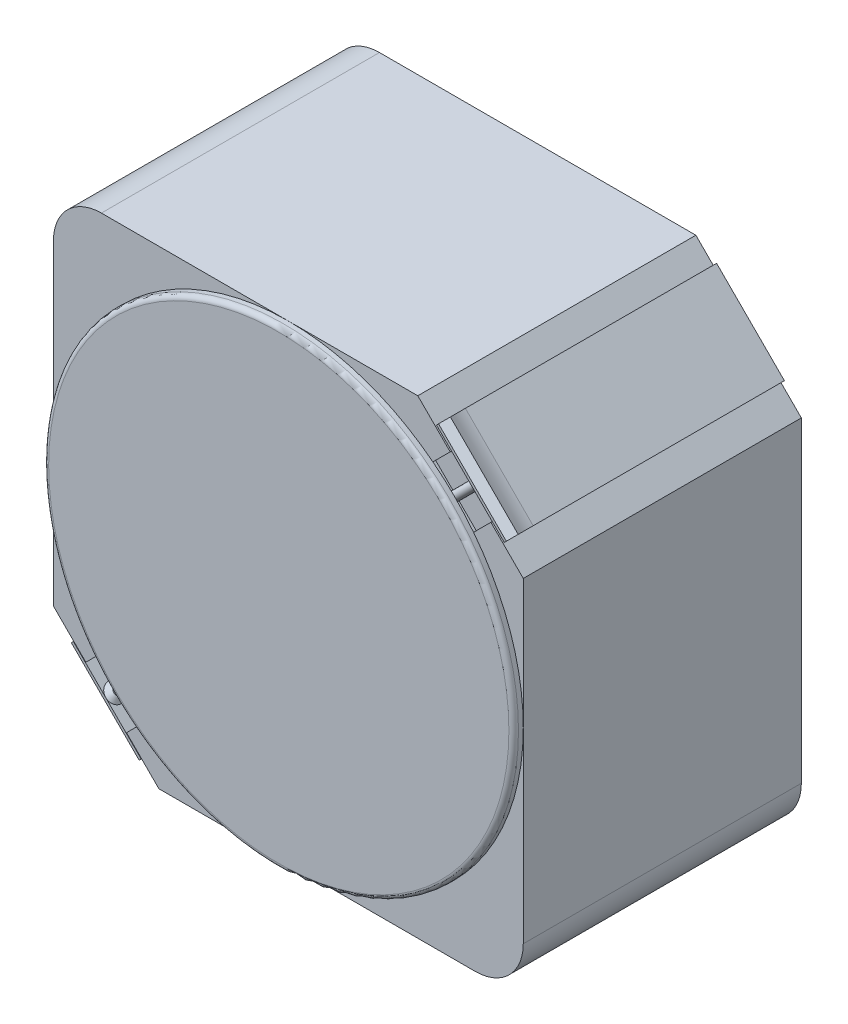
SolidWorks part; units mm, degrees
ref_plane "Спереди" through (0, 0, 0) normal (0, 0, 1) x (1, 0, 0)
ref_plane "Сверху" through (0, 0, 0) normal (0, 1, 0) x (1, 0, 0)
ref_plane "Справа" through (0, 0, 0) normal (1, 0, 0) x (0, 0, -1)
sketch "Эскиз1" plane through (0, 0, 0) normal (0, 0, 1) x (1, 0, 0)
  line L0 (-2.45, -1.35) -> (-1.35, -2.45)
  line L1 (-1.95, 2.45) -> (1.35, 2.45)
  line L2 (-2.45, 1.95) -> (-2.45, -1.35)
  line L3 (-1.35, -2.45) -> (1.95, -2.45)
  line L4 (2.45, 1.35) -> (2.45, -1.95)
  line L5 (-2.45, 2.45) -> (2.45, -2.45) construction
  line L6 (-2.45, -2.45) -> (2.45, 2.45) construction
  line L7 (1.35, 2.45) -> (2.45, 1.35)
  arc A0 (-1.95, 2.45) -> (-2.45, 1.95) centre (-1.95, 1.95) ccw
  arc A1 (1.95, -2.45) -> (2.45, -1.95) centre (1.95, -1.95) ccw
  point P0 (0, 0)
  dimension "D1" = 0.5
  dimension "D2" = 4.9
extrude "Корпус" add sketch "Эскиз1" along normal blind 2.9 from offset 0.005
sketch "Эскиз2" plane through (0, 0, 2.905) normal (0, 0, 1) x (1, 0, 0)
  line L0 (-2.45, 1.95) -> (-2.45, -1.35) construction
  circle A0 centre (0, 0) radius 2.45
extrude "Серлечник" add sketch "Эскиз2" along normal blind 0.1 and the other way blind 1
fillet "Скругление1" radius 0.05 1 edges at (2.45, 0, 3.005)
ref_plane "Плоскость1" through (0.55, -0.55, 0) normal (0.7071, -0.7071, 0) x (0, 0, 1)
sketch "Эскиз6" plane through (0.55, -0.55, 0) normal (0.7071, -0.7071, 0) x (0, 0, 1)
  line L0 (2.813, -2.782) -> (2.9, -2.73)
  line L1 (2.9, -2.7) -> (0.03, -2.7)
  line L2 (2.62, -2.73) -> (0, -2.73)
  line L3 (0, -2.73) -> (0, -2.2)
  line L4 (0.03, -2.7) -> (0.03, -2.2)
  line L5 (0.03, -2.2) -> (0, -2.2)
  line L6 (2.9, -2.73) -> (2.9, -2.7)
  line L8 (0.005, -2.687) -> (2.905, -2.687) construction
  line L9 (2.905, -2.45) -> (2.905, -1.7324) construction
  line L11 (0.005, 0.3536) -> (0.005, 2.687) construction
  line L12 (2.905, -2.687) -> (0.005, -2.687) construction
  spline S0 degree 2 poles (2.62, -2.73) (2.7238, -2.7338) (2.813, -2.782) knots 0 0 0 1 1 1
  point P8 (0, 0)
  point P15 (0, -2.73)
  point P17 (2.89, -2.566)
  point P21 (0, 0)
  point P22 (0, -2.73)
  dimension "D2" = 0.5
  dimension "D3" = 0.013
  dimension "D4" = 0.025
  dimension "D5" = 0.005
  dimension "D6" = 0.082
  dimension "D7" = 0.087
  dimension "D8" = 120.867
  dimension "D9" = 0.28
  dimension "D10" = 0.1354
  dimension "D11" = 0.0295
  dimension "D12" = 0.03
extrude "вывод, бок" add sketch "Эскиз6" against normal blind 1 from offset 0.3 offset against normal yes
ref_point "Точка1"
ref_axis "Ось1" through (0, 0, 3.005) along (0, 0, -1)
sketch "Эскиз8" plane through (0, 0, 2.905) normal (0, 0, 1) x (1, 0, 0)
  line L0 (2.1121, 1.6879) -> (1.6879, 2.1121)
  line L2 (1.6879, 2.1121) -> (1.3357, 1.76)
  line L3 (-1.6879, -2.1121) -> (-1.3357, -1.76)
  line L4 (1.5479, 1.5479) -> (0, 0) construction
  line L5 (2.1121, 1.6879) -> (1.76, 1.3357)
  line L6 (1.76, 1.3357) -> (1.3357, 1.76)
  line L7 (-1.76, -1.3357) -> (-1.3357, -1.76)
  line L8 (-2.1121, -1.6879) -> (-1.76, -1.3357)
  line L9 (-2.1121, -1.6879) -> (-1.6879, -2.1121)
  line L10 (2.45, 1.35) -> (1.35, 2.45) construction
  point P3 (1.4809, 1.4964)
  point P6 (-1.5479, 1.5479)
  dimension "D2" = 0.498
  dimension "D4" = 0.6
  dimension "D1" = 2
extrude "Вытянуть8" cut sketch "Эскиз8" against normal blind 0.2
sketch "Эскиз9" plane through (1.9092, 1.9092, 0) normal (-0.7071, -0.7071, 0) x (0, 0, 1)
  line L1 (0, 0) -> (2.804, 0) construction
  line L2 (2.9, 0.5222) -> (2.9, -0.4778) construction
  circle A0 centre (2.804, 0) radius 0.046
  point P2 (-0.2219, 0)
  point P3 (2.6811, 0)
  point P4 (2.8564, 0)
  point P5 (0, 0)
  point P6 (-3.43, -0.4201)
  point P7 (-3.5378, -0.674)
  dimension "D1" = 0.092
  dimension "D2" = 0.096
extrude "Бобышка-Вытянуть1" add sketch "Эскиз9" along normal up to next (0.511 mm away) and the other way blind 0.05 draft 45 from offset 0.05 other way draft outward yes
pattern_circular "Круговой массив3" count 2 over 360 about axis through (0, 0, 3.005) along (0, 0, -1) of "вывод, бок", "Бобышка-Вытянуть1"
sketch "Эскиз13" plane through (0, 0, 0.005) normal (0, 0, -1) x (-1, 0, 0)
  line L1 (-2.45, -1.95) -> (-2.45, 1.35) construction
  line L2 (0, -2.4) -> (0, 0) construction
  line L3 (2.45, 1.95) -> (2.45, -1.35) construction
  line L4 (1.5308, -2.2692) -> (1.35, -2.45) construction
  line L5 (1.6527, 0) -> (-1.6527, 0) construction
  line L6 (1.8, 0.7488) -> (2.4, 0.7488)
  line L7 (1.35, -2.45) -> (-1.95, -2.45) construction
  line L8 (2.4, 0.7488) -> (2.4, 1.3288)
  line L9 (1.3288, 2.4) -> (2.4, 1.3288)
  line L10 (-1.3288, 2.4) -> (1.3288, 2.4)
  line L11 (-2.4, 1.3288) -> (-1.3288, 2.4)
  line L12 (-2.4, -0.7488) -> (-1.8, -0.7488)
  line L13 (-2.4, -1.3288) -> (-2.4, -0.7488)
  line L16 (-2.4, -1.3288) -> (-1.3288, -2.4)
  line L17 (-2.4, 1.3288) -> (-2.4, 0.7488)
  line L18 (-1.3288, -2.4) -> (1.3288, -2.4)
  line L19 (1.3288, -2.4) -> (2.4, -1.3288)
  line L20 (2.4, -0.7488) -> (2.4, -1.3288)
  line L21 (1.8, -0.7488) -> (2.4, -0.7488)
  line L22 (-2.4, 0.7488) -> (-1.8, 0.7488)
  arc A0 (-1.8, -0.7488) -> (1.8, -0.7488) centre (0, 0) ccw
  arc A1 (-1.8, 0.7488) -> (1.8, 0.7488) centre (0, 0) cw
  point P3 (0, -0.7488)
  point P5 (0, -0.7488)
  point P6 (0, -0.7488)
  point P7 (0, 0)
  dimension "D5" = 0.05
  dimension "D6" = 0.0503
  dimension "D7" = 0.05
  dimension "D8" = 0.6
  dimension "D1" = 0.58
extrude "Выводы низ" add sketch "Эскиз13" along normal up to surface (0.005 mm away) up to face at (-1.7273, -1.7587, 0)
